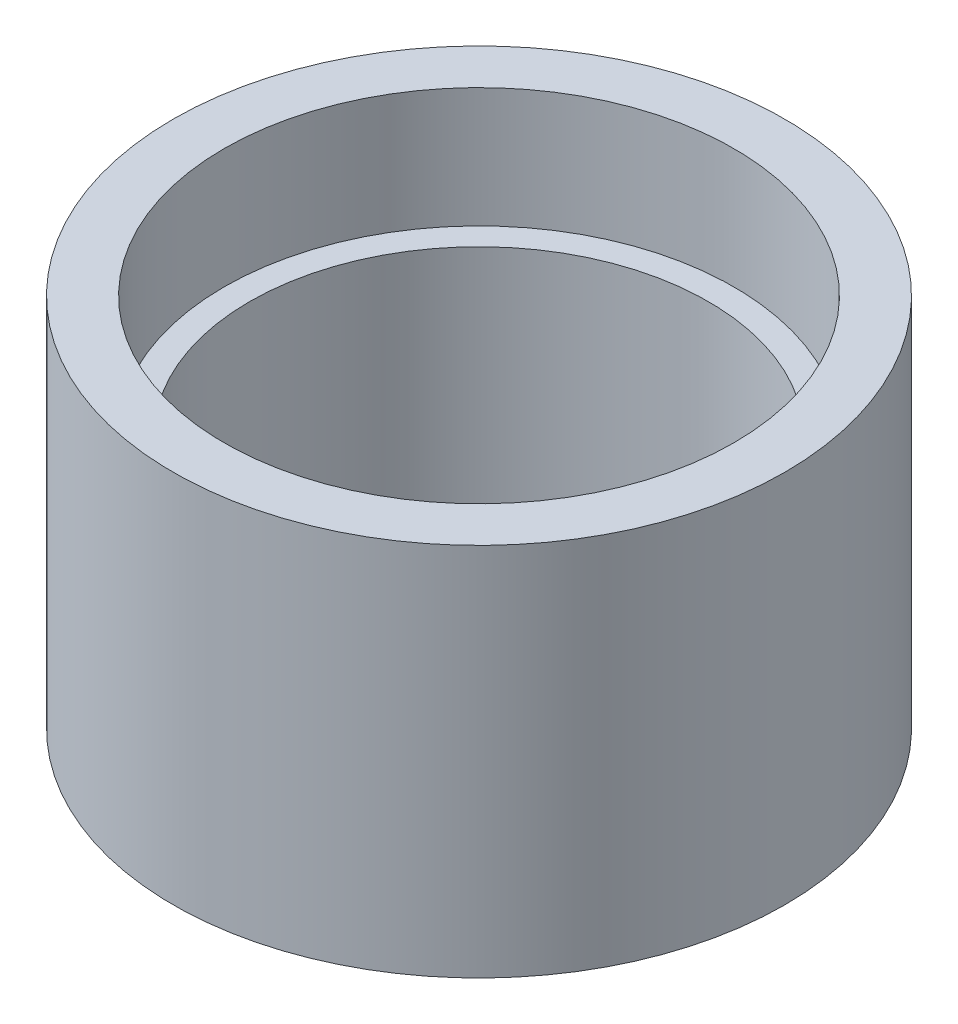
SolidWorks part; units mm, degrees
ref_plane "Front" through (0, 0, 0) normal (0, 0, 1) x (1, 0, 0)
ref_plane "Top" through (0, 0, 0) normal (0, 1, 0) x (1, 0, 0)
ref_plane "Right" through (0, 0, 0) normal (1, 0, 0) x (0, 0, -1)
ref_axis "Center Axis" through (0, 0, 55) along (0, 0, -1)
sketch "Sketch1" plane through (0, 0, 0) normal (0, 0, 1) x (1, 0, 0)
  line L1 (0, 0) -> (12, 0)
  line L2 (0, 0) -> (0, -14.7)
  line L3 (0, -14.7) -> (12, -14.7)
  line L4 (12, 0) -> (12, -14.7)
  line L5 (0, 0) -> (10, 0)
  line L6 (0, 0) -> (0, -4.7)
  line L7 (0, -4.7) -> (10, -4.7)
  line L8 (10, 0) -> (10, -4.7)
  line L9 (12, -14.7) -> (9, -14.7)
  line L10 (12, -14.7) -> (12, -4.7)
  line L11 (12, -4.7) -> (9, -4.7)
  line L12 (9, -14.7) -> (9, -4.7)
  dimension "D1" = 12
  dimension "D2" = 2
  dimension "D3" = 4.7
  dimension "D4" = 1
  dimension "D5" = 10
revolve "Revolve1" add sketch "Sketch1" angle 360 about L2 region at (11, -2.35, 0) region at (10.5, -9.7, 0)
equation "\"WallThickness\" = 2mm"
equation "\"D1@Sketch1\"=\"PiezoDiameter\"/2 +\"WallThickness\""
equation "\"PiezoDiameter\"= 20mm"
equation "\"PiezoThickness\"= 2.7mm"
equation "\"BackingThickness\"= 10mm"
equation "\"MatchingThickness\"= 2mm"
equation "\"ShelfThickness\"= 1mm"
equation "\"D2@Sketch1\"=\"WallThickness\""
equation "\"D3@Sketch1\"=\"PiezoThickness\"+\"MatchingThickness\""
equation "\"D4@Sketch1\"=\"ShelfThickness\""
equation "\"D5@Sketch1\"=\"BackingThickness\""
